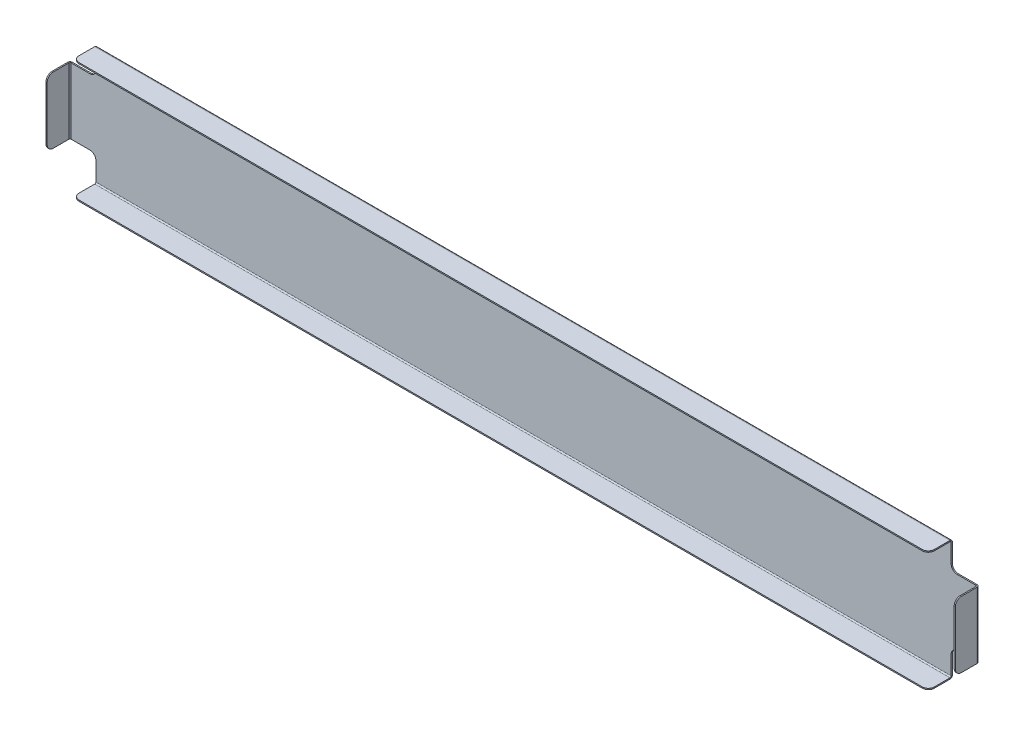
SolidWorks part; units mm, degrees
note: The reader was unsure of these and kept them because the rebuilt part matched: flange length of "Edge-Flange1".
material "ASTM A36 Steel"
ref_plane "Front Plane" through (0, 0, 0) normal (0, 0, 1) x (1, 0, 0)
ref_plane "Top Plane" through (0, 0, 0) normal (0, 1, 0) x (1, 0, 0)
ref_plane "Right Plane" through (0, 0, 0) normal (1, 0, 0) x (0, 0, -1)
sketch "Sketch1" plane through (0, 0, 0) normal (0, 0, 1) x (1, 0, 0)
  line L1 (-711.4, -100) -> (711.4, -100)
  line L2 (-756.4, -55) -> (-756.4, 55)
  line L3 (-711.4, 100) -> (711.4, 100)
  line L4 (756.4, -55) -> (756.4, 55)
  line L5 (-711.4, -136.1869) -> (711.4, 136.1869) construction
  line L6 (-711.4, 51.9554) -> (711.4, -51.9554) construction
  line L9 (-756.4, 55) -> (-711.4, 55)
  line L10 (-711.4, 100) -> (-711.4, 55)
  line L13 (-756.4, -55) -> (-711.4, -55)
  line L14 (-711.4, -100) -> (-711.4, -55)
  line L17 (756.4, 55) -> (711.4, 55)
  line L18 (711.4, 100) -> (711.4, 55)
  line L21 (756.4, -55) -> (711.4, -55)
  line L22 (711.4, -100) -> (711.4, -55)
  point P0 (0, 0)
  dimension "D1" = 1512.8
  dimension "D2" = 200
  dimension "D3" = 45
  dimension "D4" = 45
  dimension "D5" = 756.4
  dimension "D6" = 45
  dimension "D7" = 45
  dimension "D8" = 45
  dimension "D9" = 45
  dimension "D10" = 45
  dimension "D11" = 45
  dimension "D12" = 100
base flange "Base-Flange1" sketch "Sketch1" thickness 2 reverse thickness direction no parameters "D1"=0.7366
edge flange "Edge-Flange1" sketch "Sketch14" flange profiles "Sketch14", "Sketch15", "Sketch16", "Sketch17" flange angle 90 flange length 40 flange position material inside bend radius 2 thickness 2 relief rectangular parameters "D6"=10, "D8"=1
sketch "Sketch14" plane through (0, 100, 0) normal (0, 1, 0) x (-1, 0, 0)
  line L2 (-711.4, 0) -> (-711.4, 38)
  line L3 (-711.4, 38) -> (711.4, 38)
  line L4 (711.4, 38) -> (711.4, 0)
  line L7 (-711.4, 0) -> (711.4, 0) construction
  line L8 (-711.4, 0) -> (711.4, 0)
sketch "Sketch15" plane through (756.4, 0, 0) normal (1, 0, 0) x (0, 1, 0)
  line L2 (55, 0) -> (55, 38)
  line L3 (55, 38) -> (-55, 38)
  line L4 (-55, 38) -> (-55, 0)
  line L6 (-55, 0) -> (55, 0) construction
  line L7 (-55, 0) -> (55, 0)
sketch "Sketch16" plane through (0, -100, 0) normal (0, -1, 0) x (1, 0, 0)
  line L2 (711.4, 0) -> (711.4, 38)
  line L3 (711.4, 38) -> (-711.4, 38)
  line L4 (-711.4, 38) -> (-711.4, 0)
  line L6 (-711.4, 0) -> (711.4, 0) construction
  line L7 (-711.4, 0) -> (711.4, 0)
sketch "Sketch17" plane through (-756.4, 0, 0) normal (-1, 0, 0) x (0, -1, 0)
  line L2 (-55, 0) -> (-55, 38)
  line L3 (-55, 38) -> (55, 38)
  line L4 (55, 38) -> (55, 0)
  line L5 (-55, 0) -> (55, 0) construction
  line L6 (-55, 0) -> (55, 0)
bend "EdgeBend1" bend radius 2 bend angle 90 parameters "D5"=1
bend "EdgeBend2" bend radius 2 bend angle 90 parameters "D5"=2
bend "EdgeBend3" bend radius 2 bend angle 90 parameters "D5"=3
bend "EdgeBend4" bend radius 2 bend angle 90 parameters "D5"=4
fillet "Fillet1" radius 10 12 edges at (-711.4, -99, 38) (-711.4, -55, -1) (-755.4, -55, 38) (-755.4, 55, 38) (-711.4, 55, -1) (-711.4, 99, 38) (711.4, -99, 38) (711.4, -55, -1) (711.4, 99, 38) (755.4, -55, 38) (755.4, 55, 38) (711.4, 55, -1)
sketch "Bend-Lines1" [suppressed] plane through (0, 0, 0) normal (0, 1, 0) x (1, 0, 0)
sketch "Bounding-Box1" [suppressed] plane through (0, 0, 0) normal (0, 1, 0) x (1, 0, 0)
sketch "Sketch18" [suppressed] plane through (0, 0, -2) normal (0, 0, -1) x (-1, 0, 0)
  line L0 (0, 137.2546) -> (0, -137.2546)
  line L1 (793.6546, 137.2546) -> (-793.6546, 137.2546) construction
  line L2 (793.6546, -137.2546) -> (-793.6546, -137.2546) construction
  line L3 (0, -137.2546) -> (-793.6546, -137.2546)
  line L4 (-793.6546, -137.2546) -> (-793.6546, 137.2546)
  line L5 (-793.6546, 137.2546) -> (0, 137.2546)
sheet metal parameters "Sheet-Metal1" thickness 2 parameters "D1"=0.7366
flat pattern "Flat-Pattern1" [suppressed]
sketch "Bend-Lines2" plane through (0, 0, 0) normal (0, 1, 0) x (1, 0, 0)
sketch3d "Bounding-Box2" [suppressed]
  line L0 (759, -100, 0) -> (-759, -100, 0) construction
  line L1 (759, 100, 0) -> (-759, 100, 0) construction
  line L2 (759, -100, 0) -> (759, 100, 0) construction
  line L3 (-759, -100, 0) -> (-759, 100, 0) construction
sheet metal parameters "Sheet-Metal2" thickness 2 parameters "D1"=0.7366
flat pattern "Flat-Pattern1"
sketch "Bend-Lines2" plane through (0, 0, 0) normal (0, 0, 1) x (1, 0, 0)
  line L0 (-754.7562, 55) -> (-754.7562, -55) construction
  line L1 (-711.4, -98.3562) -> (711.4, -98.3562) construction
  line L2 (754.7562, -55) -> (754.7562, 55) construction
  line L3 (711.4, 98.3562) -> (-711.4, 98.3562) construction
  line L4 (-754.7562, 55) -> (-754.7562, -55) construction
  line L5 (-711.4, -98.3562) -> (711.4, -98.3562) construction
  line L6 (754.7562, -55) -> (754.7562, 55) construction
  line L7 (711.4, 98.3562) -> (-711.4, 98.3562) construction
sketch3d "Bounding-Box2" [suppressed]
  line L0 (-793.1124, -136.7124, 0) -> (793.1124, -136.7124, 0) construction
  line L1 (-793.1124, 136.7124, 0) -> (793.1124, 136.7124, 0) construction
  line L2 (-793.1124, -136.7124, 0) -> (-793.1124, 136.7124, 0) construction
  line L3 (793.1124, -136.7124, 0) -> (793.1124, 136.7124, 0) construction
bend of the flat pattern "Flatten-<EdgeBend1>1"
bend of the flat pattern "Flatten-<EdgeBend2>1"
bend of the flat pattern "Flatten-<EdgeBend3>1"
bend of the flat pattern "Flatten-<EdgeBend4>1"
